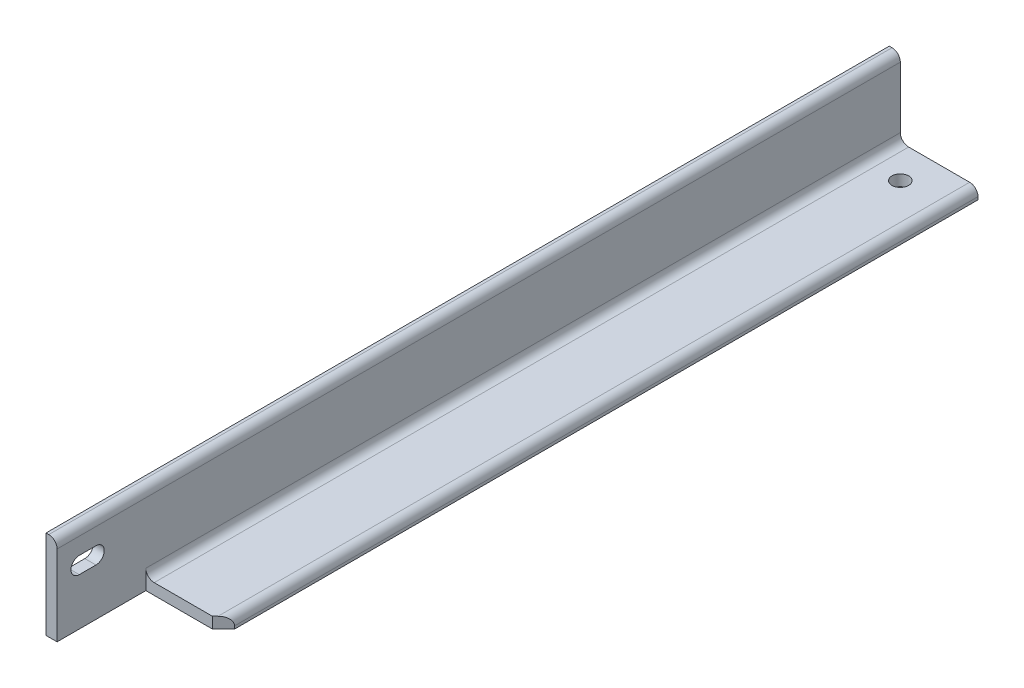
SolidWorks part; units mm, degrees
ref_plane "Front Plane" through (0, 0, 0) normal (0, 0, 1) x (1, 0, 0)
ref_plane "Top Plane" through (0, 0, 0) normal (0, 1, 0) x (1, 0, 0)
ref_plane "Right Plane" through (0, 0, 0) normal (1, 0, 0) x (0, 0, -1)
sketch "Sketch1" plane through (0, 0, 0) normal (0, 0, 1) x (1, 0, 0)
  line L0 (0, 0) -> (0, 101.6)
  line L1 (0, 101.6) -> (3.1801, 101.6)
  line L2 (12.7, 92.0801) -> (12.7, 22.225)
  line L3 (22.225, 12.7) -> (92.0801, 12.7)
  line L4 (101.6, 3.1801) -> (101.6, 0)
  line L5 (101.6, 0) -> (0, 0)
  arc A0 (101.6, 3.1801) -> (92.0801, 12.7) centre (92.0801, 3.1801) ccw
  arc A1 (3.1801, 101.6) -> (12.7, 92.0801) centre (3.1801, 92.0801) cw
  arc A2 (22.225, 12.7) -> (12.7, 22.225) centre (22.225, 22.225) cw
  circle A3 centre (0, 0) radius 9.525 construction
  dimension "D2" = 3.1801
  dimension "Radius_1" = 9.525
  dimension "Radius_2" = 9.525
  dimension "D1" = 12.7
  dimension "V_leg" = 101.6
  dimension "H_leg" = 101.6
  dimension "Thickness" = 12.7
  dimension "Flat_wid" = 3.1801
extrude "Boss-Extrude1" add sketch "Sketch1" along normal mid plane 965.2
sketch "Sketch2" plane through (0, 0, 0) normal (0, -1, 0) x (1, 0, 0)
  line L0 (88.9, 381) -> (12.7, 381)
  line L1 (101.6, 482.6) -> (101.6, -482.6) construction
  line L2 (12.7, 495.3) -> (101.6, 381) construction
  line L3 (12.7, 381) -> (12.7, 482.6)
  line L4 (12.7, 482.6) -> (101.6, 482.6)
  line L5 (101.6, 482.6) -> (101.6, 381)
  line L6 (0, 482.6) -> (0, -482.6) construction
  line L9 (88.9, 381) -> (101.6, 368.3)
  line L10 (101.6, 381) -> (101.6, 368.3)
  dimension "D1" = 12.7
  dimension "D2" = 88.9
  dimension "D3" = 101.6
  dimension "D4" = 12.7
  dimension "D5" = 101.6
  dimension "D6" = 12.7
extrude "Cut-Extrude1" cut sketch "Sketch2" against normal up to next
sketch "Sketch3" plane through (0, 0, 0) normal (-1, 0, 0) x (0, 0, 1)
  line L0 (457.2, 63.5) -> (438.15, 63.5) construction
  line L1 (457.2, 53.975) -> (438.15, 53.975)
  line L2 (457.2, 73.025) -> (438.15, 73.025)
  line L3 (482.6, 0) -> (-482.6, 0) construction
  line L4 (482.6, 101.6) -> (482.6, 0) construction
  arc A0 (457.2, 53.975) -> (457.2, 73.025) centre (457.2, 63.5) ccw
  arc A1 (438.15, 73.025) -> (438.15, 53.975) centre (438.15, 63.5) ccw
  point P2 (447.675, 63.5)
  dimension "D1" = 9.525
  dimension "D2" = 63.5
  dimension "D3" = 19.05
  dimension "D4" = 25.4
extrude "Cut-Extrude2" cut sketch "Sketch3" against normal up to next
hole_wizard "3/4 (0.75) Diameter Hole1" positions "Sketch5" profile "Sketch4" hole size "3/4" standard "Ansi Inch"
sketch "Sketch5" plane through (0, 0, 0) normal (0, -1, 0) x (1, 0, 0)
  line L0 (0, 482.6) -> (0, -482.6) construction
  line L1 (0, -482.6) -> (101.6, -482.6) construction
  point P0 (50.8, -444.5)
  dimension "D1" = 50.8
  dimension "D2" = 38.1
sketch "Sketch4" plane through (50.8, 0, -444.5) normal (1, 0, 0) x (0, 0, -1)
  line L0 (0, 0) -> (0, 56.5232)
  line L1 (0, 56.5232) -> (9.525, 50.8)
  line L2 (9.525, 50.8) -> (9.525, 0)
  line L5 (9.525, 0) -> (0, 0)
  line L10 (0, 56.5232) -> (-9.525, 50.8) construction
  line L11 (0, -6.35) -> (0, 107.95) construction
  dimension "Hole Dia." = 19.05
  dimension "Hole Depth" = 50.8
  dimension "Drill Angle" = 118
